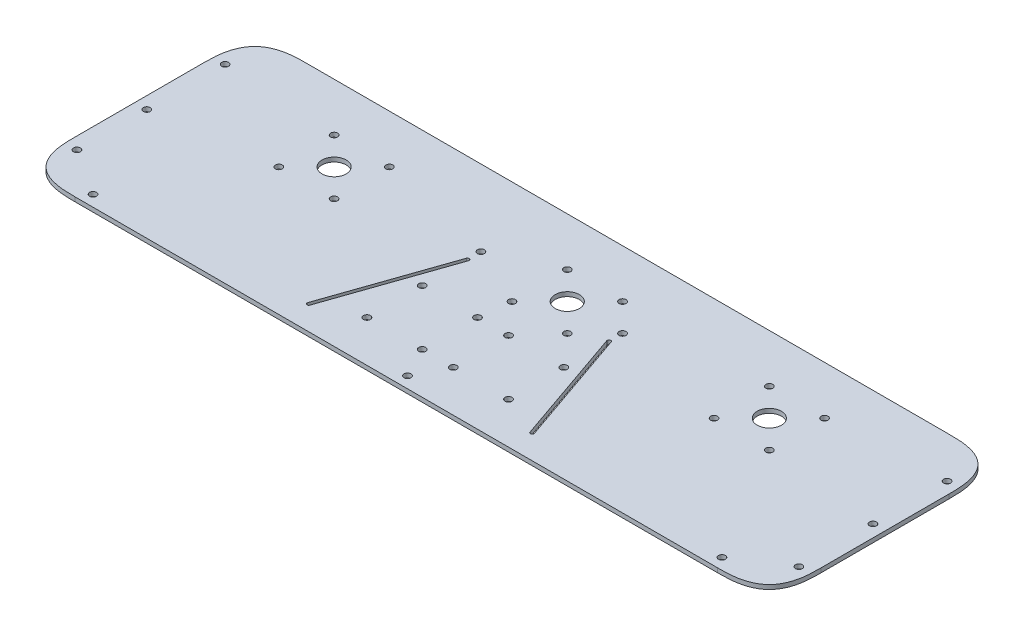
SolidWorks part; units mm, degrees
ref_plane "Front Plane" through (0, 0, 0) normal (0, 0, 1) x (1, 0, 0)
ref_plane "Top Plane" through (0, 0, 0) normal (0, 1, 0) x (1, 0, 0)
ref_plane "Right Plane" through (0, 0, 0) normal (1, 0, 0) x (0, 0, -1)
sketch "Sketch1" plane through (0, 0, 0) normal (0, 1, 0) x (1, 0, 0)
  line L1 (-103.134, 171.9149) -> (328.866, 171.9149)
  line L2 (-103.134, 171.9149) -> (-103.134, -28.0851)
  line L3 (-103.134, -28.0851) -> (328.866, -28.0851)
  line L4 (328.866, 171.9149) -> (328.866, -28.0851)
extrude "Boss-Extrude1" add sketch "Sketch1" along normal blind 2.5 contours L1 L4 L3 L2
sketch "Sketch3" plane through (0, 2.5, 0) normal (0, 1, 0) x (1, 0, 0)
  line L0 (-13.134, 71.9149) -> (-29.1359, 55.9131)
  line L1 (2.8678, 87.9167) -> (-29.1359, 87.9167)
  line L2 (2.8678, 87.9167) -> (2.8678, 55.9131)
  line L3 (2.8678, 55.9131) -> (-29.1359, 55.9131)
  line L4 (-29.1359, 87.9167) -> (-29.1359, 55.9131)
  line L5 (2.8678, 87.9167) -> (-29.1359, 55.9131) construction
  line L6 (2.8678, 55.9131) -> (-29.1359, 87.9167) construction
  line L7 (-103.134, 71.9149) -> (-13.134, 71.9149)
  line L8 (-103.134, 171.9149) -> (-103.134, -28.0851) construction
  line L9 (238.866, 71.9149) -> (238.866, 115.9149)
  line L14 (62.253, -0.3819) -> (46.2512, -16.3837)
  line L15 (238.866, 115.9149) -> (328.866, 115.9149)
  line L18 (328.866, 171.9149) -> (328.866, -28.0851) construction
  line L19 (238.866, 71.9149) -> (222.8641, 55.9131)
  line L20 (254.8678, 87.9167) -> (222.8641, 87.9167)
  line L21 (254.8678, 87.9167) -> (254.8678, 55.9131)
  line L22 (254.8678, 55.9131) -> (222.8641, 55.9131)
  line L23 (222.8641, 87.9167) -> (222.8641, 55.9131)
  line L24 (254.8678, 87.9167) -> (222.8641, 55.9131) construction
  line L25 (254.8678, 55.9131) -> (222.8641, 87.9167) construction
  line L27 (328.866, 71.9149) -> (238.866, 71.9149)
  line L28 (238.866, 115.9149) -> (238.866, 171.9149)
  line L29 (238.866, 171.9149) -> (328.866, 171.9149)
  line L30 (328.866, 115.9149) -> (328.866, 171.9149)
  line L31 (328.866, 115.9149) -> (-169.3435, 115.9149)
  line L32 (328.866, 115.9149) -> (328.866, 173.2785)
  line L33 (328.866, 173.2785) -> (-169.3435, 173.2785)
  line L34 (-169.3435, 115.9149) -> (-169.3435, 173.2785)
  line L35 (78.2549, 15.6199) -> (46.2512, 15.6199)
  line L36 (78.2549, 15.6199) -> (78.2549, -16.3837)
  line L37 (78.2549, -16.3837) -> (46.2512, -16.3837)
  line L38 (46.2512, 15.6199) -> (46.2512, -16.3837)
  line L39 (78.2549, 15.6199) -> (46.2512, -16.3837) construction
  line L40 (78.2549, -16.3837) -> (46.2512, 15.6199) construction
  circle A0 centre (-13.134, 71.9149) radius 7
  circle A1 centre (-29.1359, 55.9131) radius 2
  circle A2 centre (-29.1359, 87.9167) radius 2
  circle A3 centre (2.8678, 87.9167) radius 2
  circle A4 centre (2.8678, 55.9131) radius 2
  circle A10 centre (238.866, 71.9149) radius 7
  circle A11 centre (222.8641, 55.9131) radius 2
  circle A12 centre (222.8641, 87.9167) radius 2
  circle A13 centre (254.8678, 87.9167) radius 2
  circle A14 centre (254.8678, 55.9131) radius 2
  circle A15 centre (62.253, -0.3819) radius 7
  circle A16 centre (46.2512, -16.3837) radius 2
  circle A17 centre (46.2512, 15.6199) radius 2
  circle A18 centre (78.2549, 15.6199) radius 2
  circle A19 centre (78.2549, -16.3837) radius 2
  point P10 (328.866, 71.9149)
extrude "Cut-Extrude1" cut sketch "Sketch3" against normal blind 2.5 contours A2 | A3 | A4 | A1 | A0 | A11 | A14 | A13 | A10 | A12 | L32 L31 L34 L33
sketch "Sketch5" plane through (0, 2.5, 0) normal (0, 1, 0) x (1, 0, 0)
  line L0 (263.7413, -28.0851) -> (263.7413, -18.0851)
  line L3 (-103.134, -28.0851) -> (328.866, -28.0851) construction
  line L5 (263.7413, -18.0851) -> (328.866, -18.0851)
  line L6 (263.7413, -18.0851) -> (263.7413, -28.0851)
  line L7 (263.7413, -28.0851) -> (328.866, -28.0851)
  line L8 (328.866, -18.0851) -> (328.866, -28.0851)
  line L9 (263.7413, -18.0851) -> (-103.134, -18.0851)
  line L10 (263.7413, -18.0851) -> (263.7413, -28.0851)
  line L11 (263.7413, -28.0851) -> (-103.134, -28.0851)
  line L12 (-103.134, -18.0851) -> (-103.134, -28.0851)
  line M12 (328.866, -28.0851) -> (328.866, 115.9149)
  line M14 (-103.134, 115.9149) -> (-103.134, -28.0851)
  line M15 (-103.134, -28.0851) -> (328.866, -28.0851)
extrude "Cut-Extrude3" cut sketch "Sketch5" against normal blind 2.5 contours L0 L9 M14 M15 | L5 L0 M15 M12 region at (80.3036, 2.5, 23.0851) region at (296.3036, 2.5, 23.0851)
sketch "Sketch6" plane through (0, 2.5, 0) normal (0, 1, 0) x (1, 0, 0)
  line L0 (328.866, -18.0851) -> (-103.134, -18.0851) construction
  line L1 (112.866, -18.0851) -> (112.866, 21.9149)
  line L2 (112.866, 21.9149) -> (137.866, 21.9149)
  line L3 (112.866, 21.9149) -> (87.866, 21.9149)
  line L4 (87.866, 21.9149) -> (71.8641, 5.9131)
  line L5 (103.8678, 37.9167) -> (71.8641, 37.9167)
  line L6 (103.8678, 37.9167) -> (103.8678, 5.9131)
  line L7 (103.8678, 5.9131) -> (71.8641, 5.9131)
  line L8 (71.8641, 37.9167) -> (71.8641, 5.9131)
  line L9 (103.8678, 37.9167) -> (71.8641, 5.9131) construction
  line L10 (103.8678, 5.9131) -> (71.8641, 37.9167) construction
  line L11 (137.866, 21.9149) -> (121.8641, 5.9131)
  line L12 (153.8678, 37.9167) -> (121.8641, 37.9167)
  line L13 (153.8678, 37.9167) -> (153.8678, 5.9131)
  line L14 (153.8678, 5.9131) -> (121.8641, 5.9131)
  line L15 (121.8641, 37.9167) -> (121.8641, 5.9131)
  line L16 (153.8678, 37.9167) -> (121.8641, 5.9131) construction
  line L17 (153.8678, 5.9131) -> (121.8641, 37.9167) construction
  circle A0 centre (137.866, 21.9149) radius 16
  circle A1 centre (87.866, 21.9149) radius 16
  circle A2 centre (87.866, 21.9149) radius 7
  circle A3 centre (71.8641, 5.9131) radius 2
  circle A4 centre (71.8641, 37.9167) radius 2
  circle A5 centre (103.8678, 37.9167) radius 2
  circle A6 centre (103.8678, 5.9131) radius 2
  circle A7 centre (137.866, 21.9149) radius 7
  circle A8 centre (121.8641, 5.9131) radius 2
  circle A9 centre (121.8641, 37.9167) radius 2
  circle A10 centre (153.8678, 37.9167) radius 2
  circle A11 centre (153.8678, 5.9131) radius 2
  point P0 (112.866, -18.0851)
extrude "Cut-Extrude4" cut sketch "Sketch6" against normal blind 2.5 contours A11 | A8 | A10 | A9 | A5 | A6 | A3 | A4
sketch "Sketch8" plane through (0, 2.5, 0) normal (0, 1, 0) x (1, 0, 0)
  line L2 (153.8678, 5.9131) -> (153.8678, 90.0973)
  line L3 (153.8678, 90.0973) -> (71.8641, 90.0973)
  line L4 (71.8641, 90.0973) -> (71.8641, 5.9131)
  line L5 (153.8678, 64.0929) -> (71.8641, 64.0929)
  line L10 (177.527, -4.0851) -> (153.8678, 64.0929) construction
  line L14 (176.5823, -4.4129) -> (152.9231, 63.7651)
  line L15 (178.4718, -3.7572) -> (154.8125, 64.4208)
  line L16 (48.2049, -4.0851) -> (71.8641, 64.0929) construction
  line L17 (47.2602, -3.7572) -> (70.9194, 64.4208)
  line L18 (49.1496, -4.4129) -> (72.8089, 63.7651)
  arc A6 (176.5823, -4.4129) -> (178.4718, -3.7572) centre (177.527, -4.0851) ccw
  arc A7 (154.8125, 64.4208) -> (152.9231, 63.7651) centre (153.8678, 64.0929) ccw
  arc A8 (47.2602, -3.7572) -> (49.1496, -4.4129) centre (48.2049, -4.0851) ccw
  arc A9 (72.8089, 63.7651) -> (70.9194, 64.4208) centre (71.8641, 64.0929) ccw
  point P17 (177.527, 5.9131)
  point P18 (48.2049, 5.9131)
  point P19 (165.6974, 30.0039)
  point P22 (112.866, -4.0851)
  point P27 (60.0345, 30.0039)
extrude "Cut-Extrude5" cut sketch "Sketch8" against normal blind 2.5 contours L17 A9 L18 A8 | L15 A7 L14 A6
fillet "Fillet1" radius 30 4 edges at (-103.134, 1.25, -115.9149) (-103.134, 1.25, 18.0851) (328.866, 1.25, -115.9149) (328.866, 1.25, 18.0851) curvature continuous yes
sketch "Sketch9" plane through (0, 2.5, 0) normal (0, 1, 0) x (1, 0, 0)
  line L0 (328.866, 62.6221) -> (321.866, 62.6221)
  line L1 (328.866, 85.9149) -> (328.866, 11.9149) construction
  line L2 (321.866, 109.7214) -> (321.866, -11.8915)
  line L3 (321.866, 6.0103) -> (321.866, -11.8915)
  line L4 (321.866, 109.7214) -> (321.866, 91.8196)
  line L5 (321.866, 91.8196) -> (321.866, 109.7214)
  line L6 (-103.134, 46.4673) -> (-96.134, 46.4673)
  line L7 (-103.134, 85.9149) -> (-103.134, 11.9149) construction
  line L8 (-96.134, 46.4673) -> (-96.134, 109.7214)
  line L9 (-96.134, 109.7214) -> (-96.134, -11.8916)
  line L10 (-96.134, -11.8916) -> (-96.134, 6.0103)
  line L11 (-96.134, 109.7214) -> (-96.134, 97.3154)
  line L12 (-96.134, 109.7214) -> (-96.134, 91.8196)
  circle A0 centre (321.866, 6.0103) radius 2
  circle A1 centre (321.866, 48.9149) radius 2
  circle A2 centre (321.866, 91.8196) radius 2
  circle A3 centre (-96.134, 46.4673) radius 2
  circle A4 centre (-96.134, 91.8196) radius 2
  circle A5 centre (-96.134, 6.0103) radius 2
  spline S0 degree 2 poles (328.866, 85.9149) (328.866, 87.9765) (328.8467, 89.0459) (328.8162, 90.7467) (328.7231, 92.1742) (328.5043, 95.5283) (327.8783, 98.3317) (326.3274, 105.2776) (322.2688, 109.3319) (318.2198, 113.3765) (311.2895, 114.9258) (308.4764, 115.5546) (305.1048, 115.7733) (303.6844, 115.8655) (301.9893, 115.8958) (300.9233, 115.9149) (298.866, 115.9149) knots 0 0 0 0.0625 0.0625 0.125 0.125 0.25 0.25 0.5 0.5 0.75 0.75 0.875 0.875 0.9375 0.9375 1 1 1 construction
  spline S1 degree 2 poles (298.866, -18.0851) (300.9275, -18.0851) (301.997, -18.0659) (303.6978, -18.0353) (305.1253, -17.9422) (308.4794, -17.7234) (311.2827, -17.0975) (318.2287, -15.5466) (322.283, -11.4879) (326.3276, -7.4389) (327.8768, -0.5086) (328.5057, 2.3045) (328.7244, 5.6761) (328.8165, 7.0965) (328.8469, 8.7916) (328.866, 9.8575) (328.866, 11.9149) knots 0 0 0 0.0625 0.0625 0.125 0.125 0.25 0.25 0.5 0.5 0.75 0.75 0.875 0.875 0.9375 0.9375 1 1 1 construction
  spline S2 degree 2 poles (-73.134, 115.9149) (-75.1956, 115.9149) (-76.2651, 115.8957) (-77.9658, 115.8651) (-79.3933, 115.772) (-82.7474, 115.5532) (-85.5508, 114.9273) (-92.4967, 113.3764) (-96.551, 109.3177) (-100.5957, 105.2687) (-102.1449, 98.3384) (-102.7737, 95.5254) (-102.9924, 92.1538) (-103.0846, 90.7333) (-103.1149, 89.0383) (-103.134, 87.9723) (-103.134, 85.9149) knots 0 0 0 0.0625 0.0625 0.125 0.125 0.25 0.25 0.5 0.5 0.75 0.75 0.875 0.875 0.9375 0.9375 1 1 1 construction
  spline S3 degree 2 poles (-103.134, 11.9149) (-103.134, 9.8534) (-103.1148, 8.7839) (-103.0842, 7.0831) (-102.9911, 5.6556) (-102.7723, 2.3015) (-102.1464, -0.5019) (-100.5955, -7.4478) (-96.5368, -11.5021) (-92.4879, -15.5467) (-85.5575, -17.0959) (-82.7445, -17.7248) (-79.3729, -17.9435) (-77.9525, -18.0356) (-76.2574, -18.066) (-75.1914, -18.0851) (-73.134, -18.0851) knots 0 0 0 0.0625 0.0625 0.125 0.125 0.25 0.25 0.5 0.5 0.75 0.75 0.875 0.875 0.9375 0.9375 1 1 1 construction
extrude "Cut-Extrude6" cut sketch "Sketch9" against normal blind 2.5 contours A0 | A1 | A2 | A5 | A3 | A4
sketch "Sketch10" plane through (0, 2.5, 0) normal (0, 1, 0) x (1, 0, 0)
  line L0 (232.1904, -18.0851) -> (232.1904, -11.5851)
  line L1 (298.866, -18.0851) -> (-73.134, -18.0851) construction
  line L2 (322.1851, -11.5851) -> (-96.4532, -11.5851)
  line L3 (322.1851, -11.5851) -> (232.1904, -11.5851)
  line L4 (322.1851, -11.5851) -> (232.1904, -11.5851)
  line L5 (322.1851, -11.5851) -> (232.1904, -11.5851)
  line L6 (322.1851, -11.5851) -> (294.9418, -11.5851)
  line L7 (-96.4532, -11.5851) -> (-78.7572, -11.5851)
  line L8 (-96.4532, -11.5851) -> (-69.2097, -11.5851)
  circle A0 centre (112.866, -11.5851) radius 2
  circle A3 centre (294.9418, -11.5851) radius 2
  circle A4 centre (-69.2097, -11.5851) radius 2
  spline S0 degree 2 poles (298.866, -18.0851) (300.9275, -18.0851) (301.997, -18.0659) (303.6978, -18.0353) (305.1253, -17.9422) (308.4794, -17.7234) (311.2827, -17.0975) (318.2287, -15.5466) (322.283, -11.4879) (326.3276, -7.4389) (327.8768, -0.5086) (328.5057, 2.3045) (328.7244, 5.6761) (328.8165, 7.0965) (328.8469, 8.7916) (328.866, 9.8575) (328.866, 11.9149) knots 0 0 0 0.0625 0.0625 0.125 0.125 0.25 0.25 0.5 0.5 0.75 0.75 0.875 0.875 0.9375 0.9375 1 1 1 construction
  spline S1 degree 2 poles (-103.134, 11.9149) (-103.134, 9.8534) (-103.1148, 8.7839) (-103.0842, 7.0831) (-102.9911, 5.6556) (-102.7723, 2.3015) (-102.1464, -0.5019) (-100.5955, -7.4478) (-96.5368, -11.5021) (-92.4879, -15.5467) (-85.5575, -17.0959) (-82.7445, -17.7248) (-79.3729, -17.9435) (-77.9525, -18.0356) (-76.2574, -18.066) (-75.1914, -18.0851) (-73.134, -18.0851) knots 0 0 0 0.0625 0.0625 0.125 0.125 0.25 0.25 0.5 0.5 0.75 0.75 0.875 0.875 0.9375 0.9375 1 1 1 construction
extrude "Cut-Extrude7" cut sketch "Sketch10" against normal blind 2.5 contours A4 | A0 | A3
sketch "Sketch11" plane through (0, 2.5, 0) normal (0, 1, 0) x (1, 0, 0)
  line L0 (71.8641, 37.9167) -> (71.8641, 115.9149)
  line L1 (298.866, 115.9149) -> (-73.134, 115.9149) construction
  line L2 (153.8678, 37.9167) -> (153.8678, 115.9149)
  line L3 (-13.134, 71.9149) -> (170.9876, 71.9149)
  line L4 (121.8641, 37.9167) -> (121.8641, 95.7488)
  line L5 (121.8641, 71.9149) -> (105.8623, 55.9131)
  line L6 (137.866, 87.9167) -> (105.8623, 87.9167)
  line L7 (137.866, 87.9167) -> (137.866, 55.9131)
  line L8 (137.866, 55.9131) -> (105.8623, 55.9131)
  line L9 (105.8623, 87.9167) -> (105.8623, 55.9131)
  line L10 (137.866, 87.9167) -> (105.8623, 55.9131) construction
  line L11 (137.866, 55.9131) -> (105.8623, 87.9167) construction
  circle A1 centre (121.8641, 71.9149) radius 7
  circle A3 centre (105.8623, 55.9131) radius 2
  circle A4 centre (105.8623, 87.9167) radius 2
  circle A5 centre (137.866, 87.9167) radius 2
  circle A6 centre (137.866, 55.9131) radius 2
  circle A7 centre (153.8678, 71.9149) radius 2
  circle A9 centre (71.8641, 71.9149) radius 2
extrude "Cut-Extrude8" cut sketch "Sketch11" against normal blind 10 contours A6 | A3 | A4 | A5 | A1 | A7 | A9
ref_plane "Plane1" through (72.8089, 0, -63.7651) normal (0.3278, 0, -0.9447) x (-0.9447, 0, -0.3278)
